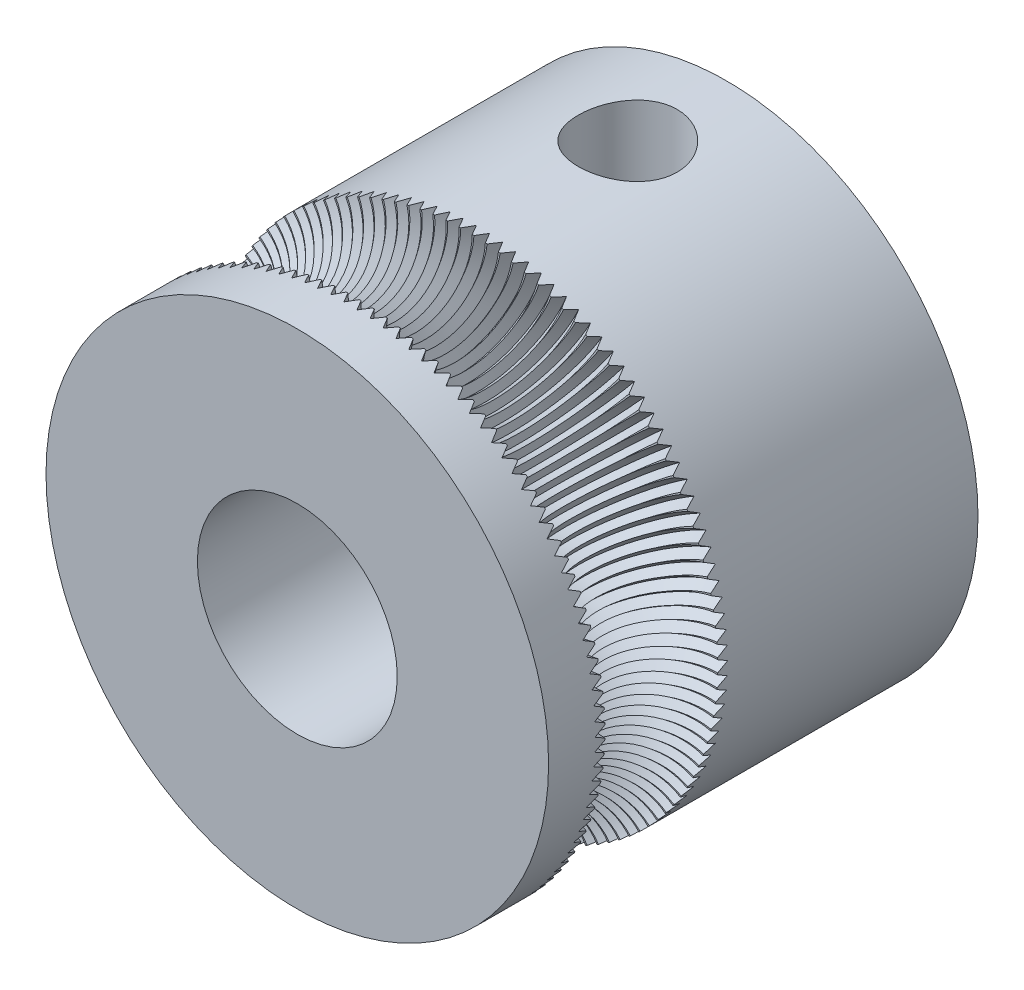
SolidWorks part; units mm, degrees
material "1.2316 (X36CrMo17)"
ref_plane "Plan de face" through (0, 0, 0) normal (0, 0, 1) x (1, 0, 0)
ref_plane "Plan de dessus" through (0, 0, 0) normal (0, 1, 0) x (1, 0, 0)
ref_plane "Plan de droite" through (0, 0, 0) normal (1, 0, 0) x (0, 0, -1)
sketch "Esquisse1" plane through (0, 0, 0) normal (0, 0, 1) x (1, 0, 0)
  circle A0 centre (0, 0) radius 2.525
  circle A1 centre (0, 0) radius 6.35
  dimension "D1" = 12.7
  dimension "D2" = 5.05
extrude "Boss.-Extru.1" add sketch "Esquisse1" along normal blind 10.85
sketch "Esquisse2" plane through (0, 0, 0) normal (1, 0, 0) x (0, 0, -1)
  line L0 (-8, 6.35) -> (-8, -6.35) construction
  line L2 (-10.85, -6.35) -> (0, -6.35) construction
  line L3 (0, 0) -> (-8, 0) construction
  circle A0 centre (-8, 6.35) radius 1.425
  dimension "D2" = 2.85
  dimension "D1" = 8
revolve "Enlèvement de matière-Révolution1" cut sketch "Esquisse2" angle 360 about L3
ref_plane "Plan1" through (0, 6.35, 0) normal (0, 1, 0) x (1, 0, 0)
sketch "Esquisse3" plane through (0, 6.35, 0) normal (0, 1, 0) x (1, 0, 0)
  line L0 (-6.35, -8) -> (6.35, -8) construction
ref_axis "Axe2" through (-6.35, 6.35, 8) along (1, 0, 0)
ref_plane "Plan2" through (0, 0, 8) normal (0, 0, 1) x (1, 0, 0)
sketch "Esquisse4" plane through (0, 0, 8) normal (0, 0, 1) x (1, 0, 0)
  line L0 (0, 0) -> (0, 6.35) construction
  line L1 (5.9675, 6.35) -> (-5.9675, 6.35) construction
  line L2 (0, 4.675) -> (-0.9671, 6.35)
  line L3 (-0.9671, 6.35) -> (0.9671, 6.35)
  line L4 (0.9671, 6.35) -> (0, 4.675)
  line L5 (0, 4.925) -> (6.35, 4.925) construction
  circle A0 centre (0, 0) radius 4.925 construction
  dimension "D1" = 0.25
  dimension "D2" = 60
revolve "Enlèvement de matière-Révolution2" cut sketch "Esquisse4" angle 360 about axis through (-6.35, 6.35, 8) along (1, 0, 0)
ref_axis "Axe3" through (0, 0, 10.85) along (0, 0, -1)
pattern_circular "Répétition circulaire1" count 120 over 360 about axis through (0, 0, 10.85) along (0, 0, -1) of "Enlèvement de matière-Révolution2"
hole_wizard "Trou taraudé M31" positions "Esquisse6" profile "Esquisse7" tap size "M3" standard "Din" end condition through all
sketch "Esquisse6" plane through (0, 0, 0) normal (0, 1, 0) x (1, 0, 0)
  line L0 (0, 0) -> (0, -10.85) construction
  line L1 (-6.35, -10.85) -> (6.35, -10.85) construction
  point P9 (0, -2.5)
  dimension "D1" = 2.5
sketch "Esquisse7" plane through (0, 0, 2.5) normal (1, 0, 0) x (0, 0, -1)
  line L0 (0, 0) -> (0, 6.35)
  line L1 (0, 6.35) -> (1.25, 6.35)
  line L2 (1.25, 6.35) -> (1.25, 0)
  line L5 (1.25, 0) -> (0, 0)
  line L11 (0, -6.35) -> (0, 107.95) construction
  dimension "Diamètre du trou pour taraudage jusqu'au prochain" = 2.5
  dimension "Profondeur du trou pour taraudage jusqu'au prochain" = 6.35
cosmetic thread "Filetage de perçage1" parameters "D2"=3
sketch "Szkic2" plane through (0, 0, 0) normal (0, 1, 0) x (1, 0, 0)
  point P1 (6.35, -8)
sketch "Szkic4" plane through (0, 0, 0) normal (0, 1, 0) x (1, 0, 0)
  circle A0 centre (0, -2.5) radius 1.25 construction
  circle A1 centre (0, -2.5) radius 1.25
  point P4 (0, -2.5)
equation "\"OutsideDiameter\"= 12.7"
equation "\"Bore\"=5.05"
equation "\"InsideDiameter\"= 11"
equation "\"GrooveDiameter\"= 2.85"
equation "\"Height\"= 10.85"
equation "\"ScrewDiameter\"= 3"
equation "\"ScrewHeight\"= 3"
equation "\"ScrewPosition\"= 2.5"
equation "\"D1@Esquisse1\"=\"OutsideDiameter\""
equation "\"D2@Esquisse1\"=\"Bore\""
equation "\"D1@Boss.-Extru.1\"=\"Height\""
equation "\"D1@Esquisse2\"=\"Height\"-\"GrooveDiameter\""
equation "\"D2@Esquisse2\"=\"GrooveDiameter\""
equation "\"D1@Plan1\"=\"OutsideDiameter\"/2"
equation "\"D1@Esquisse6\"=\"ScrewPosition\""
